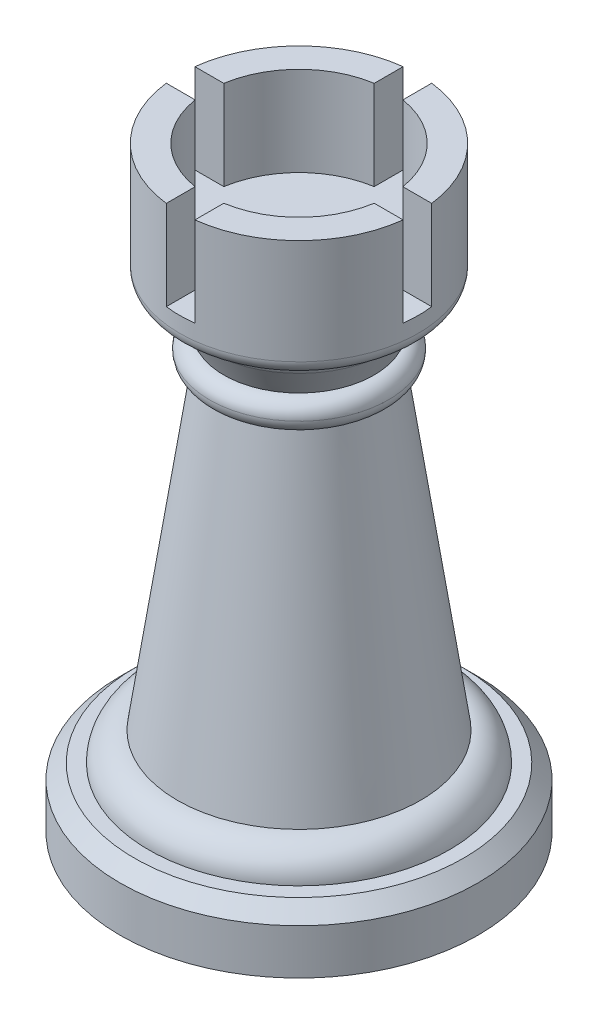
SolidWorks part; units mm, degrees
ref_plane "Front Plane" through (0, 0, 0) normal (0, 0, 1) x (1, 0, 0)
ref_plane "Top Plane" through (0, 0, 0) normal (0, 1, 0) x (1, 0, 0)
ref_plane "Right Plane" through (0, 0, 0) normal (1, 0, 0) x (0, 0, -1)
sketch "Sketch1" plane through (0, 0, 0) normal (0, 0, 1) x (1, 0, 0)
  line L0 (0, 0) -> (0, 31.75) construction
  line L1 (-6.477, 3.175) -> (-6.477, 4.699) construction
  line L2 (0, 0) -> (-9.525, 0)
  line L4 (-8.001, 3.175) -> (-9.525, 3.175)
  line L5 (-9.525, 0) -> (-9.525, 3.175)
  line L8 (-6.477, 4.699) -> (-8.001, 4.699)
  line L9 (-8.001, 3.175) -> (-8.001, 4.699)
  line L10 (-4.0386, 21.5392) -> (-9.525, 21.5392) construction
  line L11 (-6.477, 4.699) -> (-4.0386, 21.5392)
  line L12 (0, 21.5392) -> (-9.525, 21.5392) construction
  line L13 (-4.0386, 21.5392) -> (-4.7625, 21.5392)
  line L15 (-4.0005, 23.0632) -> (-4.7625, 23.0632)
  line L16 (-4.7625, 21.5392) -> (-4.7625, 23.0632)
  line L17 (-4.0005, 21.5392) -> (-4.0005, 23.0632) construction
  line L18 (-4.826, 24.638) -> (-4.0005, 23.0632)
  line L19 (0, 31.75) -> (-6.35, 31.75)
  line L21 (-4.826, 25.4) -> (-6.35, 25.4)
  line L22 (-6.35, 31.75) -> (-6.35, 25.4)
  line L26 (-4.826, 25.4) -> (-4.826, 24.638)
  line L27 (0, 0) -> (0, 31.75)
  dimension "D1" = 31.75
  dimension "D2" = 9.525
  dimension "D3" = 3.175
  dimension "D4" = 1.524
  dimension "D5" = 1.524
  dimension "D9" = 1.524
  dimension "D11" = 6.35
  dimension "D12" = 6.35
  dimension "D13" = 1.524
  dimension "D6" = 1.524
  dimension "D7" = 21.5392
revolve "Revolve1" add sketch "Sketch1" angle 360 about L0
chamfer "Chamfer1" distance 0.762 angle 45 1 edges at (0, 3.175, -9.525)
fillet "Fillet1" radius 1.524 1 edges at (0, 4.699, -8.001)
fillet "Fillet2" radius 0.762 4 edges at (0, 25.4, -4.826) (0, 25.4, -6.35) (0, 21.5392, -4.7625) (0, 23.0632, -4.7625)
fillet "Fillet3" radius 0.762 1 edges at (0, 24.638, -4.826)
sketch "Sketch3" plane through (0, 31.75, 0) normal (0, 1, 0) x (1, 0, 0)
  line L0 (-14.7411, -0.762) -> (-14.7411, 0.762)
  line L1 (0.762, 14.7411) -> (-0.762, 14.7411)
  line L2 (0.762, 14.7411) -> (0.762, -14.7411)
  line L3 (0.762, -14.7411) -> (-0.762, -14.7411)
  line L4 (-0.762, 14.7411) -> (-0.762, -14.7411)
  line L5 (0.762, 14.7411) -> (-0.762, -14.7411) construction
  line L6 (0.762, -14.7411) -> (-0.762, 14.7411) construction
  line L7 (14.7411, -0.762) -> (-14.7411, -0.762)
  line L8 (14.7411, 0.762) -> (-14.7411, 0.762)
  line L9 (14.7411, -0.762) -> (14.7411, 0.762)
  circle A3 centre (0, 0) radius 4.826
  circle A4 centre (0, 0) radius 4.826
  point P14 (0, 0)
  circle M6 centre (0, 0) radius 6.35
  dimension "D2" = 1.524
  dimension "D1" = 1.524
  dimension "D3" = 2
extrude "Cut-Extrude1" cut sketch "Sketch3" against normal blind 4.7625 contours L4 A4 L8 | L8 A4 L7 L4 | L7 A4 L4 | L2 A4 L7 | L4 A4 L2 L7 | L2 L8 L4 L7 | L2 A4 L4 L8 | L8 A4 L2 | L7 A4 L8 L2 | A4 L4 L2 M6 | A4 L7 L8 M6 | A4 L2 L4 M6 | A4 L8 L7 M6 region at (-5.5703, 31.75, 0) region at (-2.784, 31.75, 0) region at (-2.3808, 31.75, 2.3808) region at (0, 31.75, 5.5703) region at (-2.3808, 31.75, -2.3808) region at (0, 31.75, -5.5703) region at (0, 31.75, 2.784) region at (0, 31.75, 0) region at (0, 31.75, -2.784) region at (2.3808, 31.75, 2.3808) region at (2.784, 31.75, 0) region at (5.5703, 31.75, 0) region at (2.3808, 31.75, -2.3808)
